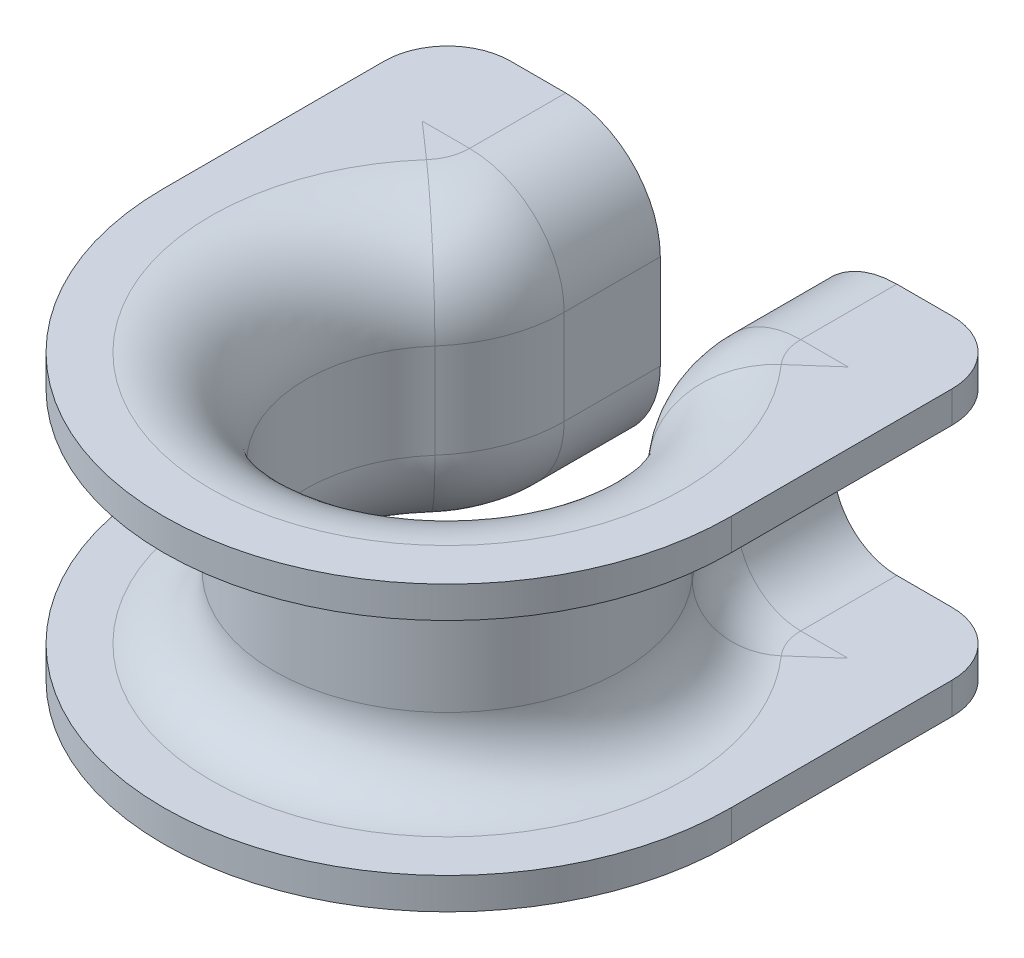
SolidWorks part; units mm, degrees
material "Polyetheretherketone (PEEK)"
ref_plane "Front Plane" through (0, 0, 0) normal (0, 0, 1) x (1, 0, 0)
ref_plane "Top Plane" through (0, 0, 0) normal (0, 1, 0) x (1, 0, 0)
ref_plane "Right Plane" through (0, 0, 0) normal (1, 0, 0) x (0, 0, -1)
sketch "Sketch1" plane through (0, 0, 0) normal (0, 1, 0) x (1, 0, 0)
  line L0 (-4.5, 11.9059) -> (-4.5, 18)
  line L1 (4.5, 11.9059) -> (4.5, 18)
  arc A0 (6.75, 5.9529) -> (-6.75, 5.9529) centre (0, 0) cw
  arc A1 (-6.75, 5.9529) -> (-4.5, 11.9059) centre (-13.5, 11.9059) ccw
  arc A2 (6.75, 5.9529) -> (4.5, 11.9059) centre (13.5, 11.9059) cw
  point P9 (0, 0)
  point P11 (-42.0844, 16.3135)
  point P12 (0, 0)
  point P13 (0, 0)
  point P14 (-3.2492, 12.8541)
  point P15 (3.7519, 10.5479)
  point P16 (0, 0)
  point P17 (2.9694, 10.795)
  point P18 (-3.2492, 18)
  dimension "D1" = 9
  dimension "D3" = 9
  dimension "D2" = 18
  dimension "D4" = 9
sketch "Sketch2" plane through (0, 0, 0) normal (1, 0, 0) x (0, 0, -1)
  line L0 (-9, -3) -> (-9, 3)
  line L1 (-15, 9) -> (-18, 9)
  line L2 (-15, -9) -> (-18, -9)
  line L5 (-15, -7) -> (-18, -7)
  line L6 (-11, -3) -> (-11, 3)
  line L7 (-15, 7) -> (-18, 7)
  line L8 (-18, 9) -> (-18, 7)
  line L9 (-18, -7) -> (-18, -9)
  arc A0 (-9, 3) -> (-15, 9) centre (-15, 3) ccw
  arc A1 (-9, -3) -> (-15, -9) centre (-15, -3) cw
  arc A2 (-11, -3) -> (-15, -7) centre (-15, -3) cw
  arc A3 (-11, 3) -> (-15, 7) centre (-15, 3) ccw
  point P3 (-9, 0)
  dimension "D1" = 3
  dimension "D2" = 6
  dimension "D3" = 18
  dimension "D4" = 2
sweep "Sweep1" add profiles "Sketch2" path "Sketch1"
sketch "Sketch7" plane through (0, 0, 0) normal (0, 1, 0) x (1, 0, 0)
  line L0 (-18, 0) -> (-18, 14)
  line L1 (-14, 18) -> (-13.5, 18)
  line L2 (-13.5, 11.9059) -> (-13.5, 18)
  line L3 (0, 0) -> (0, 18) construction
  line L4 (10.5, 18) -> (4.5, 18) construction
  line L5 (13.5, 11.9059) -> (13.5, 18)
  line L6 (14, 18) -> (13.5, 18)
  line L7 (18, 0) -> (18, 14)
  arc A0 (-13.5, 11.9059) -> (13.5, 11.9059) centre (0, 0) ccw construction
  arc A1 (-13.5, 11.9059) -> (-18, 0) centre (0, 0) ccw
  arc A2 (-18, 14) -> (-14, 18) centre (-14, 14) cw
  arc A3 (18, 14) -> (14, 18) centre (14, 14) ccw
  arc A4 (13.5, 11.9059) -> (18, 0) centre (0, 0) cw
  point P9 (0, 0)
  point P13 (1.447, 18)
  dimension "D1" = 4
extrude "Boss-Extrude1" add sketch "Sketch7" against normal up to surface (9 mm away) from surface contours A2 L0 A1 L2 L1 | L5 A4 L7 A3 L6 region at (-16.0218, 0, -12.3188) region at (16.0218, 0, -12.3188) up to face at (-12, -9, -14.9529) starting at face at (-12, -7, -14.9529)
extrude "Boss-Extrude2" add sketch "Sketch7<4>" along normal up to surface (9 mm away) from surface contours A2 L0 A1 L2 L1 | L5 A4 L7 A3 L6 region at (-16.0218, 0, -12.3188) region at (16.0218, 0, -12.3188) up to face at (-12, 9, -14.9529) starting at face at (-12, 7, -14.9529)
sketch "Sketch7<4>" plane through (0, 0, 0) normal (0, 1, 0) x (1, 0, 0) same geometry as "Sketch7"
